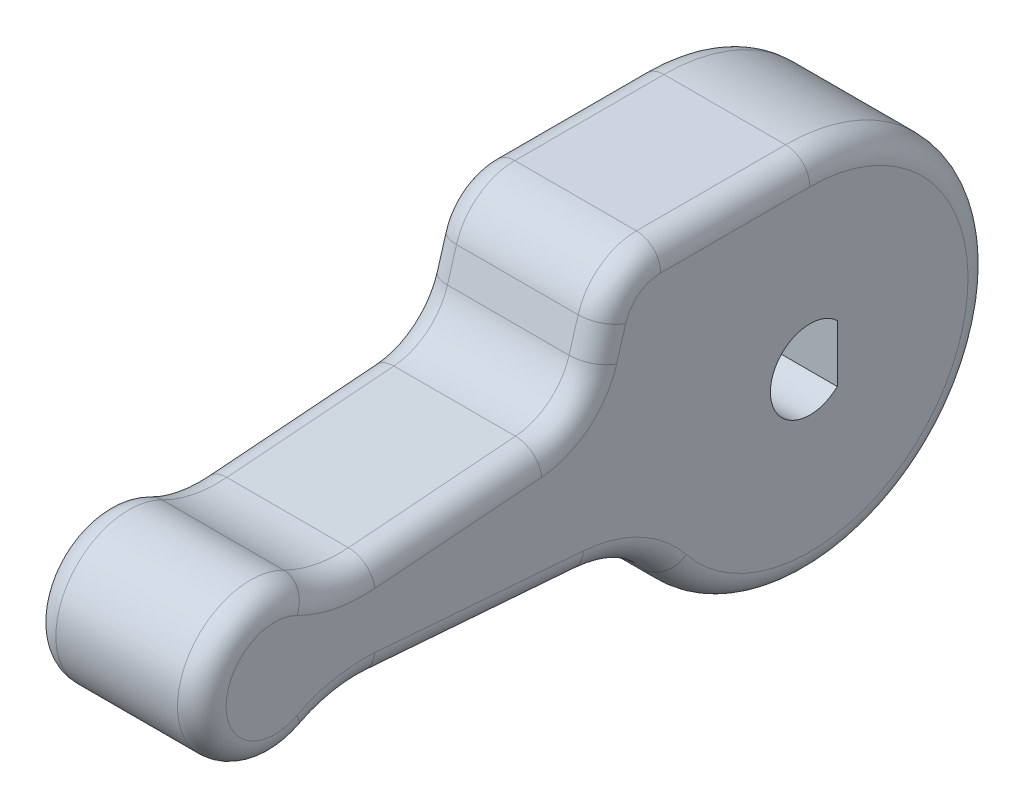
SolidWorks part; units mm, degrees
material "ABS"
ref_plane "Front Plane" through (0, 0, 0) normal (0, 0, 1) x (1, 0, 0)
ref_plane "Top Plane" through (0, 0, 0) normal (0, 1, 0) x (1, 0, 0)
ref_plane "Right Plane" through (0, 0, 0) normal (1, 0, 0) x (0, 0, -1)
sketch "Sketch1" plane through (0, 0, 0) normal (1, 0, 0) x (0, 0, -1)
  line L0 (1.125, -1.1726) -> (1.125, 1.1726)
  line L1 (-25, 0) -> (-22, 0) construction
  line L2 (-22, 0) -> (0, 0) construction
  line L3 (-19.7639, 2) -> (-6.8739, 3)
  line L4 (-19.7639, -2) -> (-6.8739, -3)
  line L5 (0, 0) -> (7.5, 0) construction
  line L6 (-1.625, 0) -> (1.125, 0) construction
  arc A0 (1.125, 1.1726) -> (1.125, -1.1726) centre (0, 0) ccw
  arc A1 (-6.8739, -3) -> (-6.8739, 3) centre (0, 0) ccw
  arc A2 (-19.7639, 2) -> (-19.7639, -2) centre (-22, 0) ccw
  dimension "D1" = 6
  dimension "D2" = 15
  dimension "D4" = 6
  dimension "D6" = 1.625
  dimension "D3" = 25
  dimension "D5" = 4
  dimension "D7" = 2.75
extrude "Boss-Extrude1" add sketch "Sketch1" along normal mid plane 7
fillet "Fillet1" radius 5 4 edges at (0, 2, 19.7639) (0, -3, 6.8739) (0, -2, 19.7639) (0, 3, 6.8739)
ref_plane "Plane1" through (0, 0, -7.625) normal (0, 0, 1) x (1, 0, 0)
hole_wizard "Hole1" positions "Sketch2" profile "Sketch3" legacy
sketch "Sketch2" plane through (0, 0, -7.625) normal (0, 0, 1) x (1, 0, 0)
  point P0 (0, 0)
sketch "Sketch3" plane through (0, 0, -7.625) normal (1, 0, 0) x (0, 1, 0)
  line L0 (0, 0) -> (0, 8)
  line L1 (0, 8) -> (1.25, 8)
  line L2 (1.25, 8) -> (1.25, 3)
  line L3 (1.25, 3) -> (1.75, 3)
  line L4 (1.75, 3) -> (1.75, 0)
  line L5 (1.75, 0) -> (0, 0)
  line L6 (0, 110) -> (0, -10) construction
  dimension "Diameter" = 2.5
  dimension "Depth" = 8
  dimension "C-Bore Diameter" = 3.5
  dimension "C-Bore Depth" = 3
sketch "Sketch4" plane through (3.5, 0, 0) normal (1, 0, 0) x (0, 0, -1)
  line L0 (0, 7.5) -> (-8, 7.5)
  line L1 (-8, 7.5) -> (-9.3891, 2.8049)
  arc A0 (-5.8655, -4.6739) -> (-5.8655, 4.6739) centre (0, 0) ccw construction
  arc A1 (-9.3891, 2.8049) -> (-5.8655, 4.6739) centre (-9.7759, 7.7899) ccw construction
  arc A2 (-9.3891, 2.8049) -> (-5.8655, 4.6739) centre (-9.7759, 7.7899) ccw
  arc A3 (0, 7.5) -> (-5.8655, 4.6739) centre (0, 0) ccw
  point P5 (-9.2303, 7.3984)
  point P8 (0, 0)
  dimension "D1" = 8
extrude "Boss-Extrude2" add sketch "Sketch4" against normal through all
fillet "Fillet3" radius 2.5 2 edges at (0, 2.8049, 9.3891) (0, 7.5, 8)
fillet "Fillet2" radius 1 22 edges at (-3.5, -3.3728, 7.4329) (-3.5, -2.4719, 13.6812) (-3.5, -2.2211, 19.341) (-3.5, 0, 25) (-3.5, 2.2211, 19.341) (-3.5, 2.4053, 14.5391) (3.5, -3.3728, 7.4329) (3.5, -2.4719, 13.6812) (3.5, -2.2211, 19.341) (3.5, 0, 25) (3.5, 2.2211, 19.341) (3.5, 2.4053, 14.5391) (-3.5, -3.2554, -6.7566) (3.5, -3.2554, -6.7566) (-3.5, 7.5, 3.0663) (3.5, 7.5, 3.0663) (-3.5, 3.2208, 9.7257) (-3.5, 5.0821, 8.7154) (-3.5, 7.0029, 7.6287) (3.5, 3.2208, 9.7257) (3.5, 5.0821, 8.7154) (3.5, 7.0029, 7.6287)
